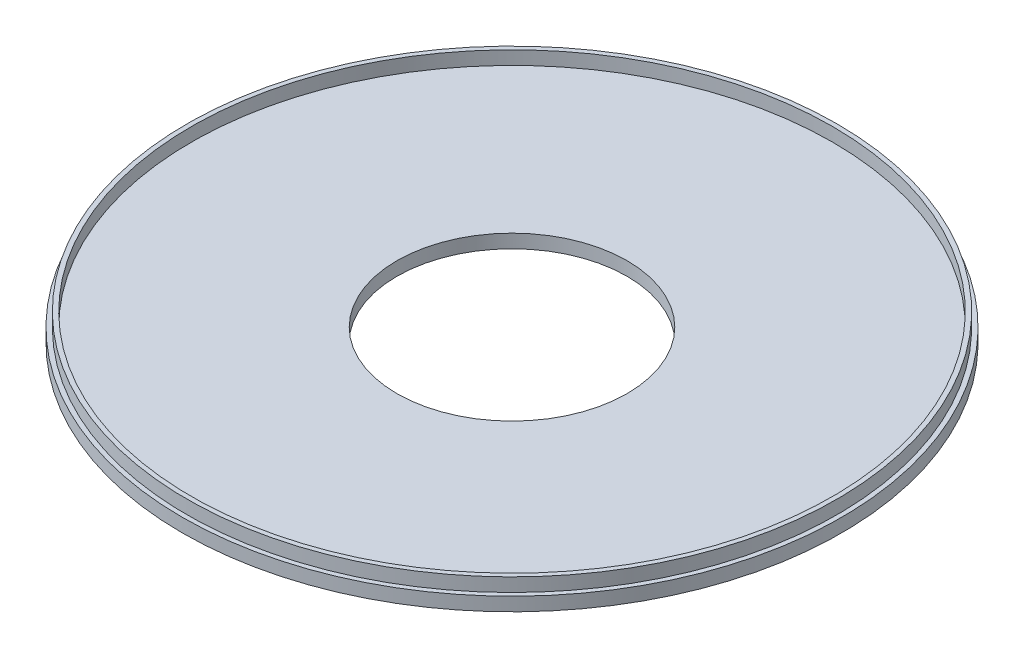
SolidWorks part; units mm, degrees
material "Silica Phenolic"
ref_plane "Piano frontale" through (0, 0, 0) normal (0, 0, 1) x (1, 0, 0)
ref_plane "Piano superiore" through (0, 0, 0) normal (0, 1, 0) x (1, 0, 0)
ref_plane "Piano destro" through (0, 0, 0) normal (1, 0, 0) x (0, 0, -1)
sketch "Schizzo1" plane through (0, 0, 0) normal (0, 0, 1) x (1, 0, 0)
  line L0 (-25.5, 0) -> (-25.5, 3)
  line L1 (-25.5, 3) -> (-71, 3)
  line L2 (-71, 3) -> (-71, 6)
  line L3 (-71, 6) -> (-72, 6)
  line L4 (-72, 6) -> (-72, 3)
  line L5 (-72, 3) -> (-73, 3)
  line L6 (-73, 3) -> (-73, 0)
  line L7 (-73, 0) -> (-25.5, 0)
  line L8 (0, 0) -> (0, 18.8486) construction
  dimension "D1" = 51
  dimension "D2" = 146
  dimension "D3" = 1
  dimension "D4" = 3
  dimension "D5" = 1
  dimension "D6" = 3
revolve "Rivoluzione1" add sketch "Schizzo1" angle 360 about L8
